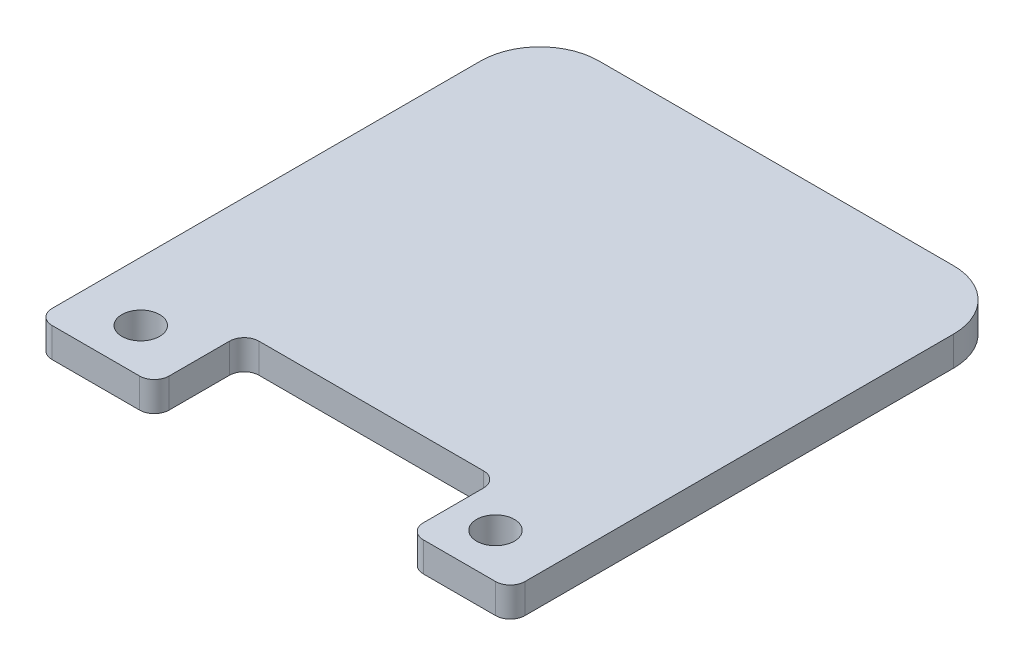
SolidWorks part; units mm, degrees
ref_plane "Front Plane" through (0, 0, 0) normal (0, 0, 1) x (1, 0, 0)
ref_plane "Top Plane" through (0, 0, 0) normal (0, 1, 0) x (1, 0, 0)
ref_plane "Right Plane" through (0, 0, 0) normal (1, 0, 0) x (0, 0, -1)
sketch "Sketch1" plane through (0, 0, 0) normal (0, 1, 0) x (1, 0, 0)
  line L1 (-25.4, 26.9875) -> (25.4, 26.9875)
  line L2 (-25.4, 26.9875) -> (-25.4, -26.9875)
  line L3 (-25.4, -26.9875) -> (25.4, -26.9875)
  line L4 (25.4, 26.9875) -> (25.4, -26.9875)
  line L5 (-25.4, 26.9875) -> (25.4, -26.9875) construction
  line L6 (-25.4, -26.9875) -> (25.4, 26.9875) construction
  point P0 (0, 0)
  dimension "D1" = 50.8
  dimension "D2" = 53.975
extrude "Boss-Extrude1" add sketch "Sketch1" along normal blind 3.175
sketch "Sketch2" plane through (0, 0, 0) normal (0, -1, 0) x (-1, 0, 0)
  line L0 (25.4, -26.9875) -> (-25.4, -26.9875) construction
  line L1 (-19.05, -22.225) -> (-25.4, -22.225) construction
  line L2 (-25.4, -26.9875) -> (-25.4, 26.9875) construction
  line L3 (19.05, -22.225) -> (25.4, -22.225) construction
  line L4 (25.4, 26.9875) -> (25.4, -26.9875) construction
  circle A0 centre (-19.05, -22.225) radius 2.032
  circle A1 centre (19.05, -22.225) radius 2.032
  dimension "D2" = 4.064
  dimension "D1" = 4.7625
  dimension "D3" = 38.1
extrude "Cut-Extrude1" cut sketch "Sketch2" against normal through all
sketch "Sketch3" plane through (0, 3.175, 0) normal (0, 1, 0) x (1, 0, 0)
  line L0 (-25.4, -26.9875) -> (25.4, -26.9875) construction
  line L1 (-12.827, -26.9875) -> (14.478, -26.9875)
  line L2 (-12.827, -26.9875) -> (-12.827, -17.3355)
  line L3 (-12.827, -17.3355) -> (14.478, -17.3355)
  line L4 (14.478, -26.9875) -> (14.478, -17.3355)
  line L5 (-25.4, 26.9875) -> (-25.4, -26.9875) construction
  dimension "D1" = 12.573
  dimension "D2" = 27.305
  dimension "D3" = 9.652
extrude "Cut-Extrude2" cut sketch "Sketch3" against normal through all
fillet "Fillet1" radius 1.5875 6 edges at (-25.4, 1.5875, 26.9875) (-12.827, 1.5875, 26.9875) (-12.827, 1.5875, 17.3355) (14.478, 1.5875, 17.3355) (14.478, 1.5875, 26.9875) (25.4, 1.5875, 26.9875)
fillet "Fillet2" radius 6.35 2 edges at (-25.4, 1.5875, -26.9875) (25.4, 1.5875, -26.9875)
